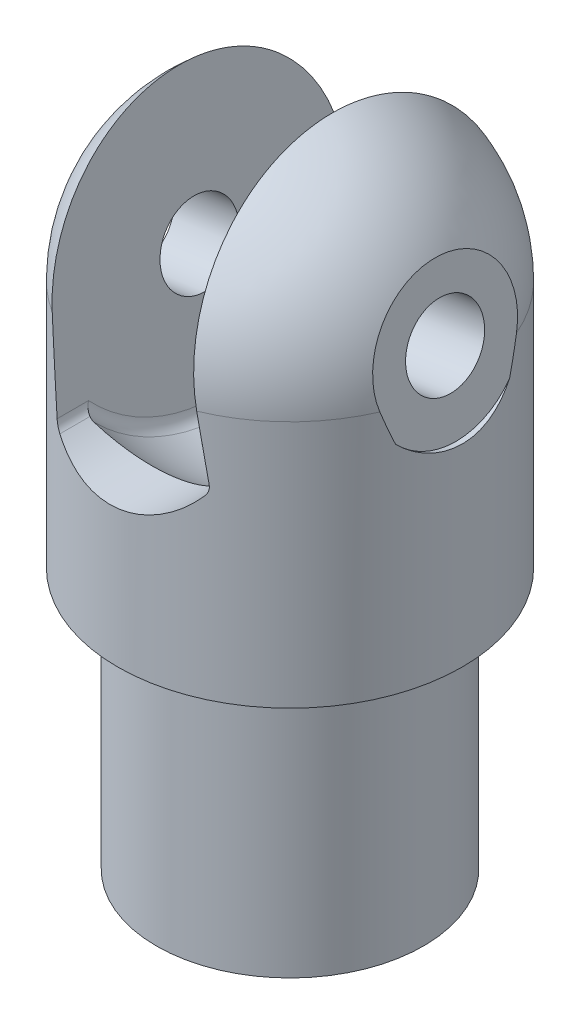
SolidWorks part; units mm, degrees
ref_plane "Front Plane" through (0, 0, 0) normal (0, 0, 1) x (1, 0, 0)
ref_plane "Top Plane" through (0, 0, 0) normal (0, 1, 0) x (1, 0, 0)
ref_plane "Right Plane" through (0, 0, 0) normal (1, 0, 0) x (0, 0, -1)
sketch "Sketch1" plane through (0, 0, 0) normal (0, 1, 0) x (1, 0, 0)
  circle A0 centre (0, 0) radius 12.9921
extrude "Boss-Extrude1" add sketch "Sketch1" along normal blind 25.4 contours A0
sketch "Sketch2" plane through (0, 0, 0) normal (1, 0, 0) x (0, 0, -1)
  line L0 (-16.764, 25.4) -> (-16.764, 49.53)
  line L1 (0, 25.4) -> (-16.764, 25.4)
  line L4 (12.9921, 25.4) -> (-12.9921, 25.4) construction
  line L5 (0, 14.2913) -> (0, -14.2913) construction
  line L6 (0, 25.4) -> (0, 66.294)
  arc A0 (0, 66.294) -> (-16.764, 49.53) centre (0, 49.53) ccw
  dimension "D1" = 33.528
  dimension "D2" = 24.13
revolve "Revolve1" add sketch "Sketch2" angle 360 about L6
ref_plane "Plane2" through (0, 49.53, 0) normal (0, -1, 0) x (-1, 0, 0)
ref_axis "Axis1" through (0, 49.53, 23.7) along (0, 0, -1)
ref_plane "Plane3" through (-6.8262, 48.5706, 0) normal (0.1392, -0.9903, 0) x (0, 0, -1)
ref_plane "Plane4" through (6.8262, 0.9594, 0) normal (-0.9903, -0.1392, 0) x (0, 0, -1)
sketch "Sketch3" plane through (-6.8556, 98.3102, 0) normal (-0.9903, -0.1392, 0) x (0, 0, -1)
  line L1 (-23.7, 49.2596) -> (13.1808, 49.2596) construction
  line L2 (0, 49.2596) -> (0, 73.1547) construction
  circle A2 centre (0, 49.2596) radius 3.81
  dimension "D1" = 7.62
extrude "Cut-Extrude1" cut sketch "Sketch3" against normal through all both and the other way through all
ref_axis "Axis2" through (17.2724, 51.9575, 0) along (-0.9903, -0.1392, 0)
sketch "Sketch10" plane through (0, 0, 0) normal (0, 0, 1) x (1, 0, 0)
  line L0 (17.2724, 51.9575) -> (-17.3227, 47.0954) construction
  line L1 (-8.8035, 48.2928) -> (6.2882, 50.4137)
  point P5 (-1.2576, 49.3533)
  dimension "D1" = 15.24
  dimension "D2" = 1.27
sketch "Sketch11" plane through (0, 0, 0) normal (0, 0, 1) x (1, 0, 0)
  line L2 (-8.8035, 48.2928) -> (6.2882, 50.4137) construction
  line L3 (-8.8035, 48.2928) -> (-11.0479, 64.2628)
  line L4 (6.2882, 50.4137) -> (3.8825, 67.5311)
  line L5 (-8.8035, 48.2928) -> (6.2882, 50.4137)
  arc A0 (3.8825, 67.5311) -> (-11.0479, 64.2628) centre (0, 49.53) ccw
  arc A1 (15.6362, 55.575) -> (-16.6967, 51.0309) centre (0, 49.53) ccw construction
  dimension "D1" = 18.415
revolve "Cut-Revolve10" cut sketch "Sketch11" angle 180 about axis through (17.2724, 51.9575, 0) along (-0.9903, -0.1392, 0) other way angle 90
sketch "Sketch13" plane through (0, 0, 0) normal (0, 0, 1) x (1, 0, 0)
  line L0 (-9.3337, 52.0657) -> (5.758, 54.1867)
  line L1 (-8.9774, 49.53) -> (-10.7815, 62.3671) construction
  line L2 (4.129, 65.7776) -> (6.4124, 49.53) construction
  line L3 (-8.8035, 48.2928) -> (6.2882, 50.4137) construction
  line L4 (-9.3337, 52.0657) -> (-11.6669, 68.667)
  line L5 (5.758, 54.1867) -> (3.4248, 70.788)
  arc A0 (3.4248, 70.788) -> (-11.6669, 68.667) centre (-1.7879, 53.1262) ccw
  dimension "D1" = 3.81
  dimension "D2" = 36.83
revolve "Cut-Revolve11" cut sketch "Sketch13" angle 360 about L0
sketch "Sketch14" plane through (0, 0, 0) normal (0, 0, 1) x (1, 0, 0)
  line L0 (-8.8035, 48.2928) -> (6.2882, 50.4137) construction
  line L1 (-8.8035, 48.2928) -> (-7.7644, 40.8994)
  line L2 (6.2882, 50.4137) -> (7.3273, 43.0204)
  line L3 (-8.8035, 48.2928) -> (6.2882, 50.4137)
  arc A0 (-7.7644, 40.8994) -> (7.3273, 43.0204) centre (-1.2576, 49.3533) ccw
  dimension "D1" = 21.336
extrude "Cut-Extrude4" cut sketch "Sketch14" along normal blind 32.004
fillet "Fillet1" radius 1.27 8 edges at (-6.9258, 34.9325, -8.8351) (-6.7798, 33.8935, 0) (-7.2001, 36.8838, 6.7827) (-7.7644, 40.8994, 13.6315) (7.3273, 43.0204, 13.7417) (7.8916, 39.0048, 6.7827) (8.3925, 35.4409, 0) (8.3694, 35.6053, -8.6699)
ref_plane "Plane5" through (-8.2655, -1.1616, 0) normal (-0.9903, -0.1392, 0) x (0, 0, -1)
sketch "Sketch15" plane through (-8.2655, -1.1616, 0) normal (-0.9903, -0.1392, 0) x (0, 0, -1)
  circle A0 centre (0, -49.048) radius 7.62
  dimension "D1" = 15.24
extrude "Cut-Extrude5" cut sketch "Sketch15" along normal blind 10.16
mirror "Mirror1" about plane through (6.8262, 0.9594, 0) normal (-0.9903, -0.1392, 0) of "Cut-Extrude5"
